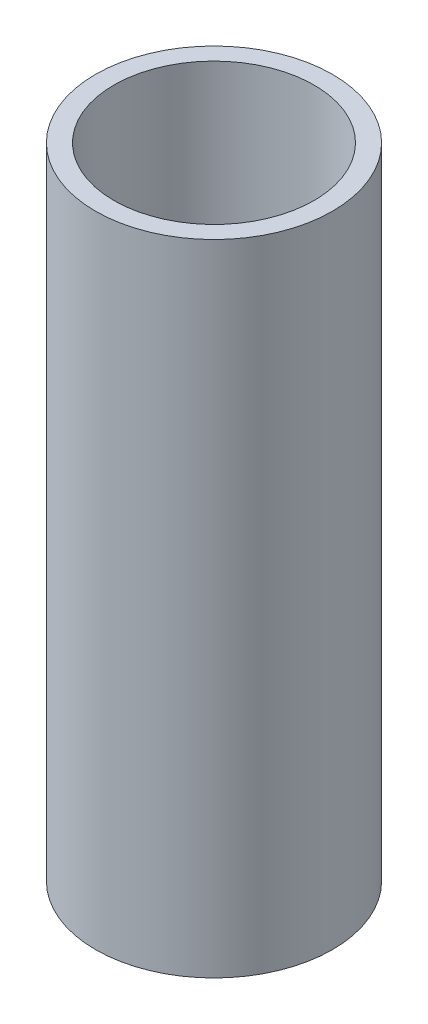
SolidWorks part; units mm, degrees
ref_plane "Front Plane" through (0, 0, 0) normal (0, 0, 1) x (1, 0, 0)
ref_plane "Top Plane" through (0, 0, 0) normal (0, 1, 0) x (1, 0, 0)
ref_plane "Right Plane" through (0, 0, 0) normal (1, 0, 0) x (0, 0, -1)
sketch "Sketch1" plane through (0, 0, 0) normal (0, 1, 0) x (1, 0, 0)
  circle A0 centre (0, 0) radius 25
  dimension "SLEEVE_OD" = 50
extrude "Boss-Extrude1" add sketch "Sketch1" along normal blind 134.8938
sketch "Sketch2" plane through (0, 0, 0) normal (0, 1, 0) x (1, 0, 0)
  circle A0 centre (0, 0) radius 21.1101
  dimension "BORE_D" = 42.2203
extrude "Cut-Extrude1" cut sketch "Sketch2" along normal through all
chamfer "Chamfer1" distance 3.1584 angle 45 rebuild error yes
